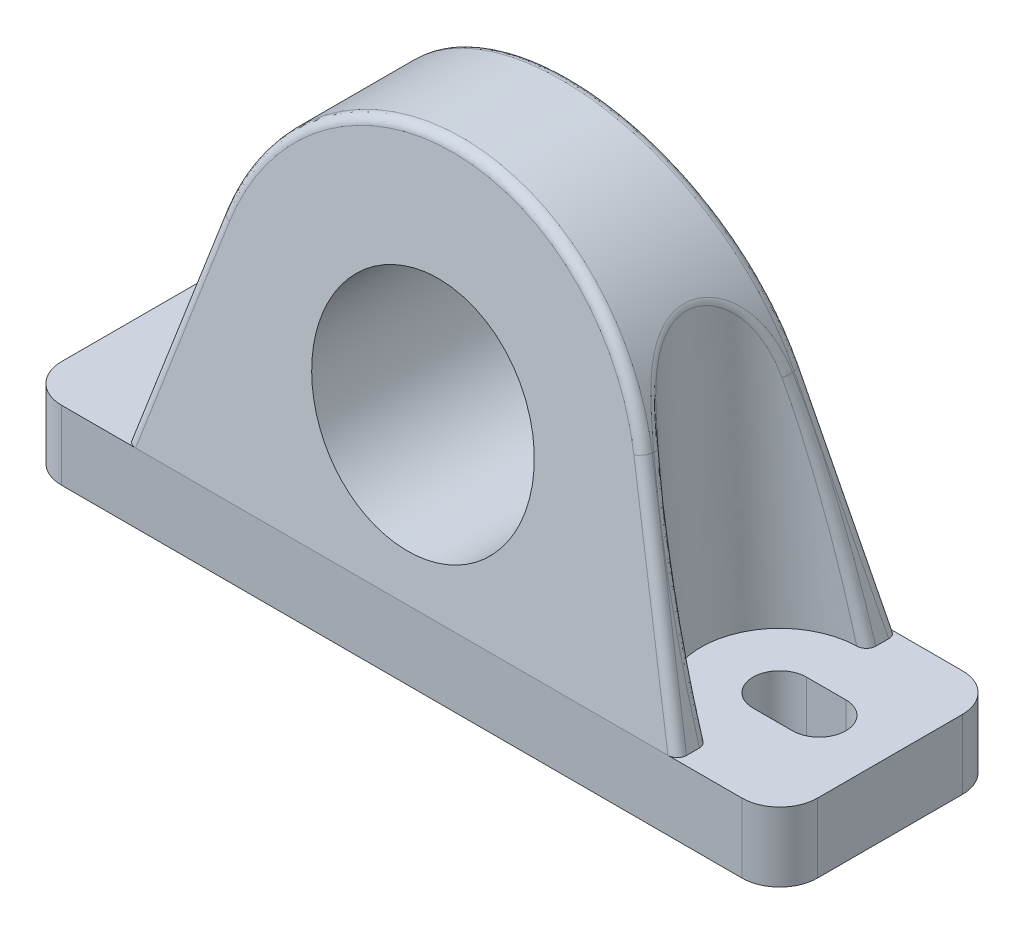
SolidWorks part; units mm, degrees
ref_plane "Front Plane" through (0, 0, 0) normal (0, 0, 1) x (1, 0, 0)
ref_plane "Top Plane" through (0, 0, 0) normal (0, 1, 0) x (1, 0, 0)
ref_plane "Right Plane" through (0, 0, 0) normal (1, 0, 0) x (0, 0, -1)
sketch "Sketch1" plane through (0, 0, 0) normal (0, 1, 0) x (1, 0, 0)
  line L1 (-120, -35) -> (120, -35)
  line L2 (-120, -35) -> (-120, 35)
  line L3 (-120, 35) -> (120, 35)
  line L4 (120, -35) -> (120, 35)
  line L5 (-120, -35) -> (120, 35) construction
  line L6 (-120, 35) -> (120, -35) construction
  point P0 (0, 0)
  dimension "D1" = 240
  dimension "D2" = 70
extrude "Boss-Extrude1" add sketch "Sketch1" along normal blind 22
sketch "Sketch2" plane through (0, 0, 0) normal (0, 0, 1) x (1, 0, 0)
  line L0 (0, 0) -> (0, 70) construction
  line L1 (-67.043, 90.1305) -> (-87.5, 22)
  line L2 (-120, 22) -> (120, 22) construction
  line L3 (67.043, 90.1305) -> (87.5, 22)
  line L4 (-87.5, 22) -> (87.5, 22)
  circle A1 centre (0, 70) radius 35
  arc A2 (67.043, 90.1305) -> (-67.043, 90.1305) centre (0, 70) ccw
  point P1 (0, 0)
  point P7 (0, 22)
  point P12 (-33.2046, 58.934)
  point P13 (72.2164, 53.3831)
  point P14 (-39.499, 46.0211)
  point P15 (0, 0)
  point P16 (0, 0)
  dimension "D1" = 70
  dimension "D4" = 70
  dimension "D2" = 70
  dimension "D3" = 175
extrude "Boss-Extrude2" add sketch "Sketch2" along normal mid plane 70
sketch "Sketch3" plane through (0, 22, 0) normal (0, 1, 0) x (1, 0, 0)
  line L1 (-85, 0) -> (85, 0) construction
  circle A0 centre (-85, 0) radius 25
  point P5 (74.7289, 0)
  point P6 (0, 0)
  dimension "D1" = 50
  dimension "D2" = 170
sketch "Sketch4" plane through (0, 0, 0) normal (0, 0, 1) x (1, 0, 0)
  line L0 (-87.5, 22) -> (-80.778, 150.2638)
  line L1 (-87.5, 22) -> (-87.5, 152.1002) construction
  point P3 (-82.2665, 121.8604)
  point P4 (-87.5, 152.1002)
  point P6 (-80.778, 150.2638)
  dimension "D1" = 3
sweep "Cut-Sweep1" cut profiles "Sketch3" path "Sketch4"
mirror "Mirror1" about plane through (0, 0, 0) normal (1, 0, 0) of "Cut-Sweep1"
sketch "Sketch5" plane through (0, 0, 0) normal (1, 0, 0) x (0, 0, -1)
  line L0 (-35, 22) -> (-18.4162, 140)
  line L1 (35, 140) -> (-35, 140) construction
  line L2 (-35, 22) -> (-35, 140)
  line L3 (-35, 140) -> (-35, 90.1305) construction
  line L4 (-18.4162, 140) -> (-35, 140)
  dimension "D1" = 8
extrude "Cut-Extrude2" cut sketch "Sketch5" against normal through all both and the other way through all
mirror "Mirror2" about plane through (0, 0, 0) normal (0, 0, 1) of "Cut-Extrude2"
fillet "Fillet1" radius 12 4 edges at (-120, 11, -35) (-120, 11, 35) (120, 11, -35) (120, 11, 35)
fillet "Fillet2" radius 3 12 edges at (80.3274, 45.8876, 24.7649) (81.3687, 42.4197, -24.8685) (55.3001, 112.9174, -1.7997) (77.2715, 56.0652, 30.2124) (77.2715, 56.0652, -30.2124) (0, 140, 18.4162) (-77.2715, 56.0652, 30.2124) (-81.3687, 42.4197, 24.8685) (-80.3274, 45.8876, -24.7649) (-55.3001, 112.9174, 1.7997) (-77.2715, 56.0652, -30.2124) (0, 140, -18.4162)
sketch "Sketch6" plane through (0, 22, 0) normal (0, 1, 0) x (1, 0, 0)
  line L0 (-85, 0) -> (-97.5, 0) construction
  line L3 (-85, -8.5) -> (-97.5, -8.5)
  line L6 (-85, 8.5) -> (-97.5, 8.5)
  line L7 (0, 0) -> (0, 68.3744) construction
  line L8 (85, 0) -> (97.5, 0) construction
  line L9 (85, -8.5) -> (97.5, -8.5)
  line L10 (85, 8.5) -> (97.5, 8.5)
  arc A4 (-85, -8.5) -> (-85, 8.5) centre (-85, 0) ccw
  arc A5 (-97.5, 8.5) -> (-97.5, -8.5) centre (-97.5, 0) ccw
  arc A6 (85, -8.5) -> (85, 8.5) centre (85, 0) cw
  arc A7 (97.5, 8.5) -> (97.5, -8.5) centre (97.5, 0) cw
  point P3 (-91.25, 0)
  point P9 (91.25, 0)
  dimension "D3" = 17
  dimension "D1" = 85
  dimension "D2" = 97.5
extrude "Cut-Extrude3" cut sketch "Sketch6" against normal through all and the other way through all
